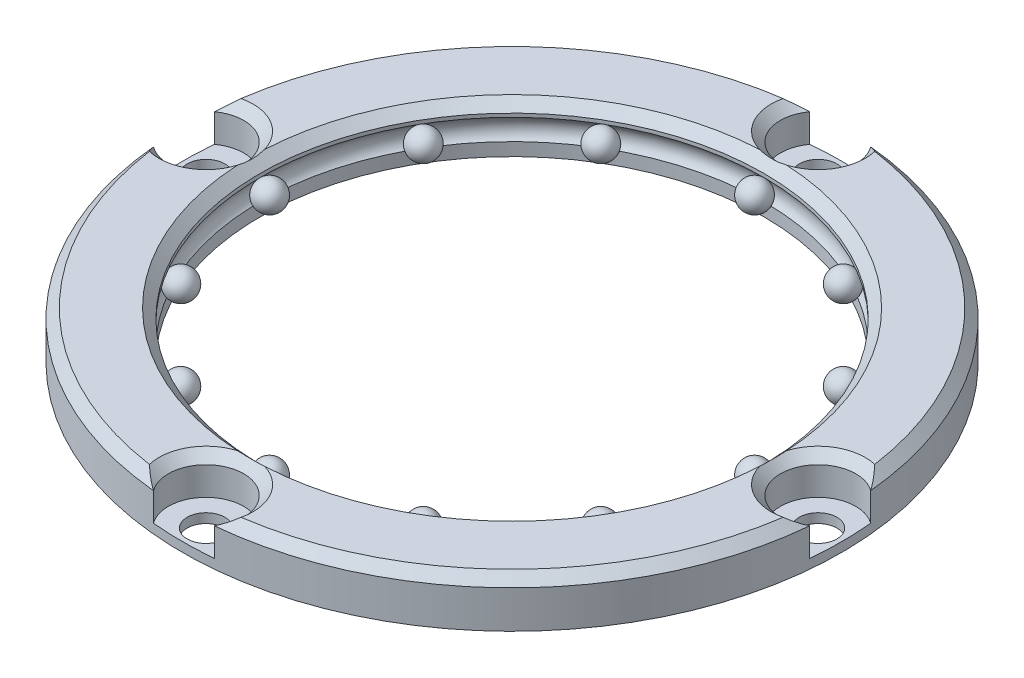
SolidWorks part; units mm, degrees
material "1023 Carbon Steel Sheet (SS)"
ref_plane "Front Plane" through (0, 0, 0) normal (0, 0, 1) x (1, 0, 0)
ref_plane "Top Plane" through (0, 0, 0) normal (0, 1, 0) x (1, 0, 0)
ref_plane "Right Plane" through (0, 0, 0) normal (1, 0, 0) x (0, 0, -1)
sketch "Sketch1" plane through (0, 0, 0) normal (0, 1, 0) x (1, 0, 0)
  line L0 (0, 0) -> (0, 19) construction
  circle A1 centre (0, 19) radius 8.5 construction
  circle A2 centre (19, 0) radius 3
  circle A3 centre (19, 0) radius 1.5313
  circle A5 centre (0, 19) radius 10 construction
  circle A10 centre (0, 19) radius 3
  circle A12 centre (0, -19) radius 3
  circle A14 centre (0, 19) radius 1.5313
  circle A17 centre (0, -19) radius 1.5313
  circle A18 centre (-19, 0) radius 3
  circle A19 centre (-19, 0) radius 1.5313
  point P13 (0, 0)
  point P24 (0, 0)
  point P26 (0, 0)
  point P30 (0, 0)
  dimension "D5" = 17
  dimension "D7" = 6
  dimension "D8" = 3.0625
  dimension "D2" = 19
  dimension "D3" = 19
  dimension "D6" = 19
sketch "Sketch2" plane through (0, 0, 0) normal (0, 1, 0) x (-1, 0, 0)
  line L0 (0, 0) -> (-13.435, 13.435) construction
  circle A0 centre (0, 0) radius 23.75
  circle A2 centre (0, 0) radius 19 construction
  circle A3 centre (-13.435, 13.435) radius 2.5
  circle A4 centre (13.435, 13.435) radius 2.5
  circle A8 centre (0, 0) radius 1.5875
  circle A9 centre (13.435, -13.435) radius 2.5
  circle A10 centre (0, 19) radius 2.5
  circle A11 centre (19, 0) radius 2.5
  circle A12 centre (0, -19) radius 2.5
  circle A13 centre (-19, 0) radius 2.5
  circle A14 centre (-13.435, -13.435) radius 2.5
  point P19 (0, 0)
  point P27 (0, 0)
  dimension "D1" = 3.175
  dimension "D2" = 47.5
  dimension "D4" = 5
  dimension "D6" = 5
  dimension "D3" = 4
  dimension "D5" = 4
extrude "Boss-Extrude2" add sketch "Sketch2" against normal blind 5 contours A0 A11 A10 A8 region at (23.0782, 0, 0)
sketch "Sketch3" plane through (0, 0, 0) normal (0, 1, 0) x (1, 0, 0)
  circle A0 centre (0, 19) radius 3.45
  circle A1 centre (19, 0) radius 3.45
  circle A2 centre (0, -19) radius 3.45
  circle A3 centre (-19, 0) radius 3.45
  point P12 (0, 0)
  dimension "D1" = 6.9
  dimension "D2" = 4
extrude "Cut-Extrude1" cut sketch "Sketch3" against normal blind 4
sketch "Sketch4" plane through (0, 0, 0) normal (0, 0, 1) x (1, 0, 0)
  line L0 (-23.75, -5) -> (-23.75, 0) construction
  line L1 (-23.75, 0) -> (-23.75, -5) construction
  line L2 (-23.75, 0) -> (-24.75, 0) construction
  line L3 (-27.75, 0) -> (-27.75, -5) construction
  line L4 (-27.75, -5) -> (-25.75, -5) construction
  line L5 (-23.75, -5) -> (-24.75, -5) construction
  line L6 (-25.75, -5) -> (-25.75, 0) construction
  line L7 (-25.75, -1.95) -> (-25.75, 0) construction
  line L8 (-24.75, 0) -> (-23.75, 0)
  line L11 (-23.75, -2.5) -> (-17.0406, -2.5) construction
  line L12 (-23.75, -5) -> (-24.75, -5) construction
  line L14 (-24.75, -5) -> (-23.75, -5)
  line L15 (-25.75, -3.05) -> (-25.75, -5) construction
  line L16 (-24.75, 0) -> (-24.75, -1.382)
  line L17 (-24.75, -5) -> (-24.75, -3.618)
  line L18 (-25.75, 0) -> (-27.75, 0) construction
  line L19 (-24.75, -5) -> (-23.75, -5) construction
  line L20 (-25.75, -5) -> (-27.75, -5) construction
  line L21 (-26.75, -5) -> (-26.75, -3.618)
  line L22 (-26.75, 0) -> (-26.75, -1.382)
  line L23 (-26.75, 0) -> (-35, 0)
  line L24 (-35, 0) -> (-35, -5)
  line L25 (-35, -5) -> (-26.75, -5)
  line L26 (23.75, -2.5) -> (-23.75, -2.5) construction
  line L27 (23.75, 0) -> (-23.75, 0) construction
  line L28 (23.75, -5) -> (23.75, 0) construction
  line L29 (0, -2.5) -> (0, 0) construction
  line L30 (-23.75, -2.5) -> (-35, -2.5) construction
  line L31 (-23.75, 0) -> (-23.75, -5)
  arc A5 (-26.75, -1.382) -> (-26.75, -3.618) centre (-25.75, -2.5) ccw
  arc A6 (-24.75, -3.618) -> (-24.75, -1.382) centre (-25.75, -2.5) ccw
  dimension "D1" = 1.5
  dimension "D3" = 1
  dimension "D2" = 2
  dimension "D4" = 35
revolve "Revolve1" add sketch "Sketch4" angle 360 about L29
sketch "Sketch5" plane through (0, 0, 0) normal (0, 1, 0) x (1, 0, 0)
  circle A0 centre (0, 0) radius 32.5 construction
  circle A1 centre (0, 32.5) radius 2
  circle A2 centre (32.5, 0) radius 2
  circle A3 centre (0, -32.5) radius 2
  circle A4 centre (-32.5, 0) radius 2
  point P14 (0, 0)
  dimension "D1" = 4
extrude "Cut-Extrude2" cut sketch "Sketch5" against normal blind 10
sketch "Sketch6" plane through (0, 0, 0) normal (0, 1, 0) x (1, 0, 0)
  circle A0 centre (0, -32.5) radius 4
  circle A1 centre (-32.5, 0) radius 4
  circle A2 centre (0, 32.5) radius 4
  circle A3 centre (32.5, 0) radius 4
  point P12 (0, 0)
  dimension "D1" = 8
extrude "Cut-Extrude3" cut sketch "Sketch6" against normal blind 4
chamfer "Chamfer2" distance 1 angle 45 9 edges at (0, 0, -26.75) (-28.5, 0, 0) (-24.7487, 0, -24.7487) (0, 0, -28.5) (24.7487, 0, -24.7487) (28.5, 0, 0) (24.7487, 0, 24.7487) (0, 0, 28.5) (-24.7487, 0, 24.7487)
sketch "Sketch7" plane through (0, 0, 0) normal (0, 1, 0) x (1, 0, 0)
  circle A0 centre (0, 0) radius 24.75
  circle A1 centre (13.435, 13.435) radius 2.5
  circle A2 centre (13.435, 13.435) radius 2.5
  circle A3 centre (-13.435, 13.435) radius 2.5
  circle A4 centre (-13.435, 13.435) radius 2.5
  circle A5 centre (0, 0) radius 1.5875
  circle A6 centre (0, 0) radius 1.5875
  circle A7 centre (-13.435, -13.435) radius 2.5
  circle A8 centre (-13.435, -13.435) radius 2.5
  circle A9 centre (13.435, -13.435) radius 2.5
  circle A10 centre (13.435, -13.435) radius 2.5
  circle A11 centre (-19, 0) radius 3.45
  circle A12 centre (-19, 0) radius 3.45
  circle A13 centre (0, -19) radius 3.45
  circle A14 centre (0, -19) radius 3.45
  circle A15 centre (19, 0) radius 3.45
  circle A16 centre (19, 0) radius 3.45
  circle A17 centre (0, 19) radius 3.45
  circle A18 centre (0, 19) radius 3.45
  dimension "D1" = 0
  dimension "D2" = 0
  dimension "D3" = 0
  dimension "D4" = 0
  dimension "D5" = 0
  dimension "D6" = 0
  dimension "D7" = 0
  dimension "D8" = 0
  dimension "D9" = 0
extrude "Boss-Extrude3" add sketch "Sketch7" along normal blind 0.25
chamfer "Chamfer3" distance 0.5 angle 45 10 edges at (0, 0.25, -15.55) (0, 0.25, 22.45) (13.435, 0.25, 15.935) (0, 0.25, 1.5875) (13.435, 0.25, -10.935) (0, 0.25, 24.75) (-13.435, 0.25, -10.935) (-13.435, 0.25, 15.935) (-19, 0.25, 3.45) (19, 0.25, 3.45)
sketch "Sketch8" plane through (0, 0, 0) normal (0, 0, 1) x (1, 0, 0)
  line L0 (25.75, -2.5) -> (0, -2.5) construction
  line L3 (-35, -5) -> (35, -5) construction
  line L4 (-26.75, -5) -> (26.75, -5) construction
  line L5 (26.75, -5) -> (24.75, -5) construction
  line L6 (-24.75, -5) -> (24.75, -5) construction
  line L10 (25.75, -1) -> (25.75, -4)
  arc A0 (25.75, -1) -> (25.75, -4) centre (25.75, -2.5) ccw
  dimension "D1" = 25.75
  dimension "D2" = 1.5
  dimension "D3" = 2.5
revolve "Revolve2" add sketch "Sketch8" angle 360 about L10
pattern_circular "CirPattern1" count 12 over 360 about axis through (0, -5, 0) along (0, 1, 0) of bodies 121
delete or keep bodies "Body-Delete/Keep 1" type delete bodies bodies 119
